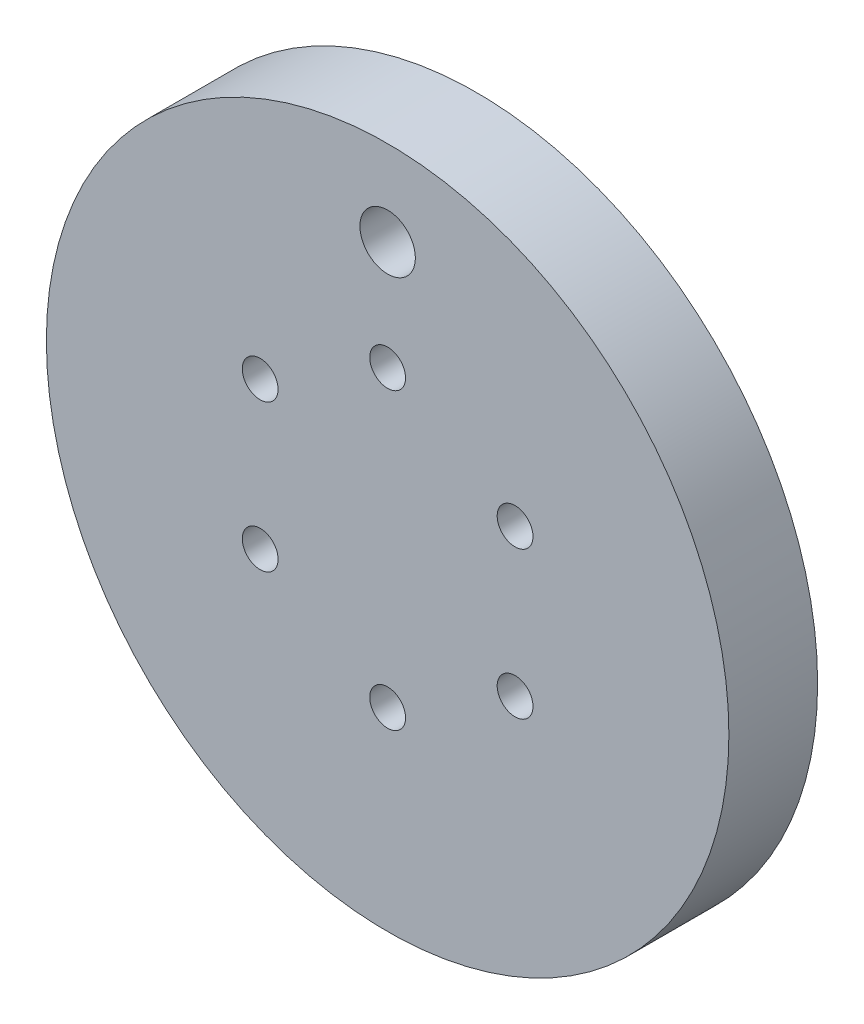
SolidWorks part; units mm, degrees
ref_plane "前视基准面" through (0, 0, 0) normal (0, 0, 1) x (1, 0, 0)
ref_plane "上视基准面" through (0, 0, 0) normal (0, 1, 0) x (1, 0, 0)
ref_plane "右视基准面" through (0, 0, 0) normal (1, 0, 0) x (0, 0, -1)
other "Configuration Table"
sketch "草图1" plane through (0, 0, 0) normal (0, 0, 1) x (1, 0, 0)
  circle A0 centre (0, 0) radius 40
  circle A1 centre (0, 17.25) radius 2.1
  circle A2 centre (14.9389, 8.625) radius 2.1
  circle A3 centre (14.9389, -8.625) radius 2.1
  circle A4 centre (0, -17.25) radius 2.1
  circle A5 centre (-14.9389, -8.625) radius 2.1
  circle A6 centre (-14.9389, 8.625) radius 2.1
  point P17 (0, 0)
  dimension "D1" = 80
  dimension "D2" = 4.2
  dimension "D3" = 17.25
  dimension "D4" = 6
extrude "凸台-拉伸1" add sketch "草图1" along normal blind 10.4 contours A0 | A6 | A5 | A4 | A3 | A2 | A1
sketch "草图2" plane through (0, 0, 10.4) normal (0, 0, 1) x (1, 0, 0)
  circle A0 centre (0, 30) radius 3.25
  circle A1 centre (0, 0) radius 40
  circle A2 centre (0, 0) radius 40
  dimension "D2" = 30
  dimension "D3" = 6.5
  dimension "D1" = 0
extrude "切除-拉伸1" cut sketch "草图2" against normal through all contours A0
